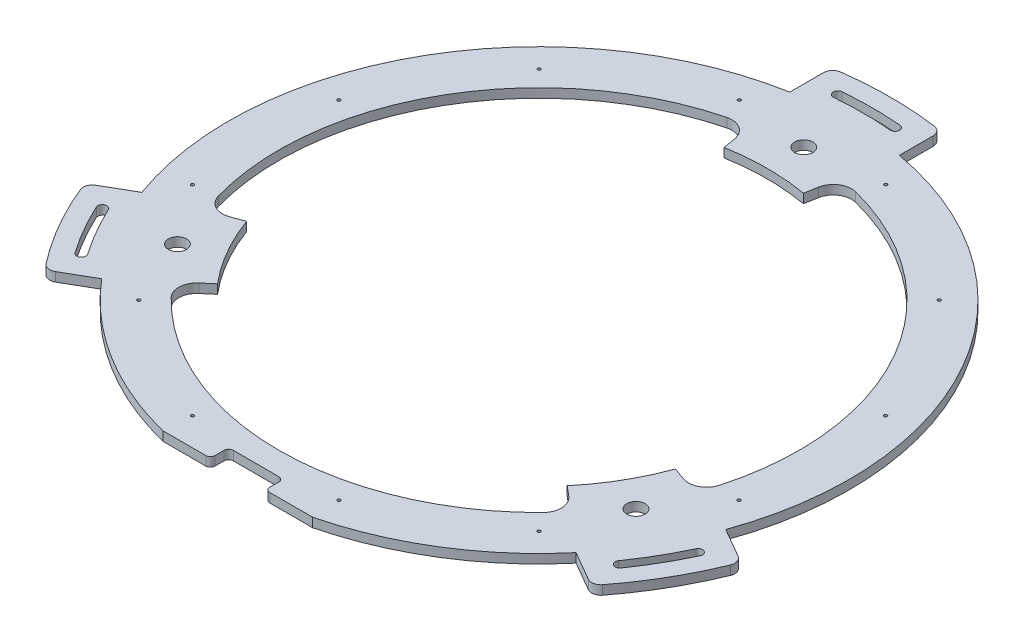
SolidWorks part; units mm, degrees
ref_plane "Front Plane" through (0, 0, 0) normal (0, 0, 1) x (1, 0, 0)
ref_plane "Top Plane" through (0, 0, 0) normal (0, 1, 0) x (1, 0, 0)
ref_plane "Right Plane" through (0, 0, 0) normal (1, 0, 0) x (0, 0, -1)
sketch "Sketch1" plane through (0, 0, 0) normal (0, 1, 0) x (1, 0, 0)
  circle A0 centre (0, 0) radius 250
  circle A1 centre (0, 0) radius 340
  circle A3 centre (0, 0) radius 340 construction
  dimension "D1" = 500
extrude "Boss-Extrude1" add sketch "Sketch1" along normal blind 10
sketch "Sketch2" plane through (0, 0, 0) normal (0, -1, 0) x (1, 0, 0)
  line L0 (0, 0) -> (549.798, 317.426) construction
  line L1 (0, 0) -> (604.1918, 0) construction
  line L2 (351.8598, 133.8643) -> (319.8275, 115.3705)
  line L3 (291.8598, 237.7874) -> (259.8275, 219.2935)
  line L4 (298.9905, 209.3554) -> (290.799, 203.6196) construction
  arc A0 (304.7761, 235.2372) -> (356.1094, 146.3252) centre (0, 0) cw
  circle A1 centre (0, 0) radius 340 construction
  arc A2 (291.8598, 237.7874) -> (304.7761, 235.2372) centre (296.8598, 229.1271) cw
  arc A3 (356.1094, 146.3252) -> (351.8598, 133.8643) centre (346.8598, 142.5246) cw
  arc A4 (298.9905, 209.3554) -> (330.8023, 154.2557) centre (0, 0) cw
  arc A5 (321.7393, 150.0295) -> (290.799, 203.6196) centre (0, 0) ccw
  arc A6 (298.9905, 209.3554) -> (290.799, 203.6196) centre (294.8947, 206.4875) ccw
  arc A7 (330.8023, 154.2557) -> (321.7393, 150.0295) centre (326.2708, 152.1426) cw
  arc A29 (319.8275, 115.3705) -> (259.8275, 219.2935) centre (0, 0) ccw
  point P12 (299.3459, 242.1095)
  point P15 (359.3459, 138.1864)
  dimension "D2" = 10
  dimension "D3" = 10
  dimension "D4" = 360
  dimension "D5" = 385
  dimension "D1" = 30
  dimension "D6" = 60
  dimension "D7" = 5
extrude "Boss-Extrude2" add sketch "Sketch2" against normal blind 10
pattern_circular "CirPattern1" count 3 over 360 about axis through (0, 0, 0) along (0, 1, 0) of "Boss-Extrude2"
sketch "Sketch6" plane through (0, 10, 0) normal (0, 1, 0) x (1, 0, 0)
  line L4 (248.3083, -90.3768) -> (234.9232, -85.505) construction
  line L5 (43.412, 246.2019) -> (0, 0) construction
  line L6 (60, 334.664) -> (60, 371.6517)
  line L7 (-60, 371.6517) -> (-60, 334.664)
  line L8 (-319.8275, -115.3705) -> (-351.8598, -133.8643)
  line L9 (-291.8598, -237.7874) -> (-259.8275, -219.2935)
  line L10 (259.8275, -219.2935) -> (291.8598, -237.7874)
  line L11 (351.8598, -133.8643) -> (319.8275, -115.3705)
  line L12 (60, 334.664) -> (60, 371.6517)
  line L13 (248.3083, -90.3768) -> (234.9232, -85.505)
  line L14 (-319.8275, -115.3705) -> (-351.8598, -133.8643)
  line L15 (-291.8598, -237.7874) -> (-259.8275, -219.2935)
  line L16 (0, 0) -> (234.9232, -85.505) construction
  line L17 (43.412, 246.2019) -> (45.8855, 260.2297)
  line L18 (-226.3788, -253.6782) -> (-48.5351, -412.3834)
  line L19 (-226.3788, -253.6782) -> (-48.5351, -412.3834)
  line L20 (-28.5605, -420) -> (28.5605, -420)
  line L21 (-28.5605, -420) -> (28.5605, -420)
  line L22 (48.5351, -412.3834) -> (226.3788, -253.6782)
  line L23 (48.5351, -412.3834) -> (226.3788, -253.6782)
  arc A5 (70.5312, 276.1346) -> (45.8855, 260.2297) centre (65.5817, 256.7568) ccw construction
  arc A6 (248.3083, -90.3768) -> (274.4052, -76.9855) centre (255.1487, -71.583) ccw
  arc A7 (274.4052, -76.9855) -> (70.5312, 276.1346) centre (0, 0) ccw
  arc A8 (70.5312, 276.1346) -> (45.8855, 260.2297) centre (65.5817, 256.7568) ccw
  arc A9 (43.412, 246.2019) -> (234.9232, -85.505) centre (0, 0) cw
  arc A12 (319.8275, -115.3705) -> (60, 334.664) centre (0, 0) ccw
  arc A13 (60, 371.6517) -> (51.3333, 381.5624) centre (50, 371.6517) ccw
  arc A14 (51.3333, 381.5624) -> (-51.3333, 381.5624) centre (0, 0) ccw
  arc A15 (-51.3333, 381.5624) -> (-60, 371.6517) centre (-50, 371.6517) ccw
  arc A16 (-60, 334.664) -> (-319.8275, -115.3705) centre (0, 0) ccw
  arc A17 (-351.8598, -133.8643) -> (-356.1094, -146.3252) centre (-346.8598, -142.5246) ccw
  arc A18 (-356.1094, -146.3252) -> (-304.7761, -235.2372) centre (0, 0) ccw
  arc A19 (-304.7761, -235.2372) -> (-291.8598, -237.7874) centre (-296.8598, -229.1271) ccw
  arc A20 (-259.8275, -219.2935) -> (259.8275, -219.2935) centre (0, 0) ccw
  arc A21 (291.8598, -237.7874) -> (304.7761, -235.2372) centre (296.8598, -229.1271) ccw
  arc A22 (304.7761, -235.2372) -> (356.1094, -146.3252) centre (0, 0) ccw
  arc A23 (356.1094, -146.3252) -> (351.8598, -133.8643) centre (346.8598, -142.5246) ccw
  arc A24 (28.5605, -420) -> (48.5351, -412.3834) centre (28.5605, -390) ccw
  arc A25 (60, 371.6517) -> (51.3333, 381.5624) centre (50, 371.6517) ccw
  arc A26 (51.3333, 381.5624) -> (-51.3333, 381.5624) centre (0, 0) ccw
  arc A27 (-51.3333, 381.5624) -> (-60, 371.6517) centre (-50, 371.6517) ccw
  arc A28 (-60, 334.664) -> (-319.8275, -115.3705) centre (0, 0) ccw
  arc A29 (-351.8598, -133.8643) -> (-356.1094, -146.3252) centre (-346.8598, -142.5246) ccw
  arc A30 (-356.1094, -146.3252) -> (-304.7761, -235.2372) centre (0, 0) ccw
  arc A31 (-304.7761, -235.2372) -> (-291.8598, -237.7874) centre (-296.8598, -229.1271) ccw
  arc A32 (-259.8275, -219.2935) -> (259.8275, -219.2935) centre (0, 0) ccw
  arc A33 (226.3788, -253.6782) -> (-226.3788, -253.6782) centre (0, 0) ccw
  arc A34 (226.3788, -253.6782) -> (-226.3788, -253.6782) centre (0, 0) ccw
  arc A35 (28.5605, -420) -> (48.5351, -412.3834) centre (28.5605, -390) ccw
  arc A36 (-48.5351, -412.3834) -> (-28.5605, -420) centre (-28.5605, -390) ccw
  arc A37 (-48.5351, -412.3834) -> (-28.5605, -420) centre (-28.5605, -390) ccw
  circle M37 centre (0, 0) radius 250
  dimension "D3" = 100
  dimension "D1" = 0
  dimension "D2" = 0
extrude "Cut-Extrude1" cut sketch "Sketch6" against normal blind 10 contours A7 A8 L13 A6 M37 region at (243.1223, 10, 83.8016)
pattern_circular "CirPattern2" count 3 over 360 about axis through (0, 0, 0) along (0, 1, 0) of "Cut-Extrude1"
sketch "Sketch7" plane through (0, 0, 0) normal (0, -1, 0) x (1, 0, 0)
  line L0 (-81.8535, 330) -> (81.8535, 330)
  arc A0 (259.8275, 219.2935) -> (-259.8275, 219.2935) centre (0, 0) ccw construction
  arc A1 (81.8535, 330) -> (-81.8535, 330) centre (0, 0) ccw
  dimension "D1" = 330
extrude "Cut-Extrude2" cut sketch "Sketch7" against normal blind 10
sketch "Sketch8" plane through (0, 10, 0) normal (0, 1, 0) x (1, 0, 0)
  line L0 (0, 0) -> (0, 290) construction
  circle A0 centre (0, 290) radius 10
  circle A1 centre (251.1474, -145) radius 10
  circle A2 centre (-251.1474, -145) radius 10
  arc A3 (-60, 334.664) -> (-319.8275, -115.3705) centre (0, 0) ccw construction
  point P10 (0, 0)
  dimension "D1" = 20
  dimension "D2" = 290
  dimension "D3" = 3
extrude "Cut-Extrude3" cut sketch "Sketch8" against normal blind 10
sketch "Sketch9" plane through (0, 10, 0) normal (0, 1, 0) x (1, 0, 0)
  line L0 (0, 0) -> (0, -330) construction
  line L1 (-81.8535, -330) -> (81.8535, -330) construction
  line L2 (30, -330) -> (30, -310)
  line L3 (30, -310) -> (-30, -310)
  line L4 (-30, -330) -> (-30, -310)
  line L5 (-30, -330) -> (30, -330)
  point P9 (0, -310)
  dimension "D1" = 60
  dimension "D2" = 310
extrude "Cut-Extrude4" cut sketch "Sketch9" against normal blind 10
fillet "Fillet1" radius 5 4 edges at (30, 5, 330) (30, 5, 310) (-30, 5, 310) (-30, 5, 330)
hole_wizard "CSK for M3 Flat Head Machine Screw1" positions "Sketch10" profile "Sketch11" countersink size "M3" standard "ANSI Metric" end condition through all
sketch "Sketch10" plane through (0, 40, 0) normal (0, 1, 0) x (1, 0, 0)
  line L0 (80.2339, 299.437) -> (0, 0) construction
  line L2 (0, 0) -> (0, 423.7069) construction
  circle A0 centre (0, 0) radius 310 construction
  point P0 (80.2339, 299.437)
  point P21 (219.2031, 219.2031)
  point P22 (299.437, 80.2339)
  point P23 (299.437, -80.2339)
  point P24 (219.2031, -219.2031)
  point P25 (80.2339, -299.437)
  point P26 (-80.2339, -299.437)
  point P27 (-219.2031, -219.2031)
  point P28 (-299.437, -80.2339)
  point P29 (-299.437, 80.2339)
  point P30 (-219.2031, 219.2031)
  point P31 (-80.2339, 299.437)
  point P32 (0, 0)
sketch "Sketch11" plane through (80.2339, 40, -299.437) normal (1, 0, 0) x (0, 0, 1)
  line L0 (0, 0) -> (0, 40)
  line L1 (0, 40) -> (1.7, 40)
  line L2 (1.7, 40) -> (1.7, 1.45)
  line L3 (1.7, 1.45) -> (3.15, 0)
  line L4 (3.15, 0) -> (0, 0)
  line L5 (-1.7, 1.45) -> (-3.15, 0) construction
  line L6 (0, -6.35) -> (0, 107.95) construction
  dimension "Thru Hole Dia." = 3.4
  dimension "Thru Hole Depth" = 40
  dimension "Near C'Sink Dia." = 6.3
  dimension "Near C'Sink Angle" = 90
